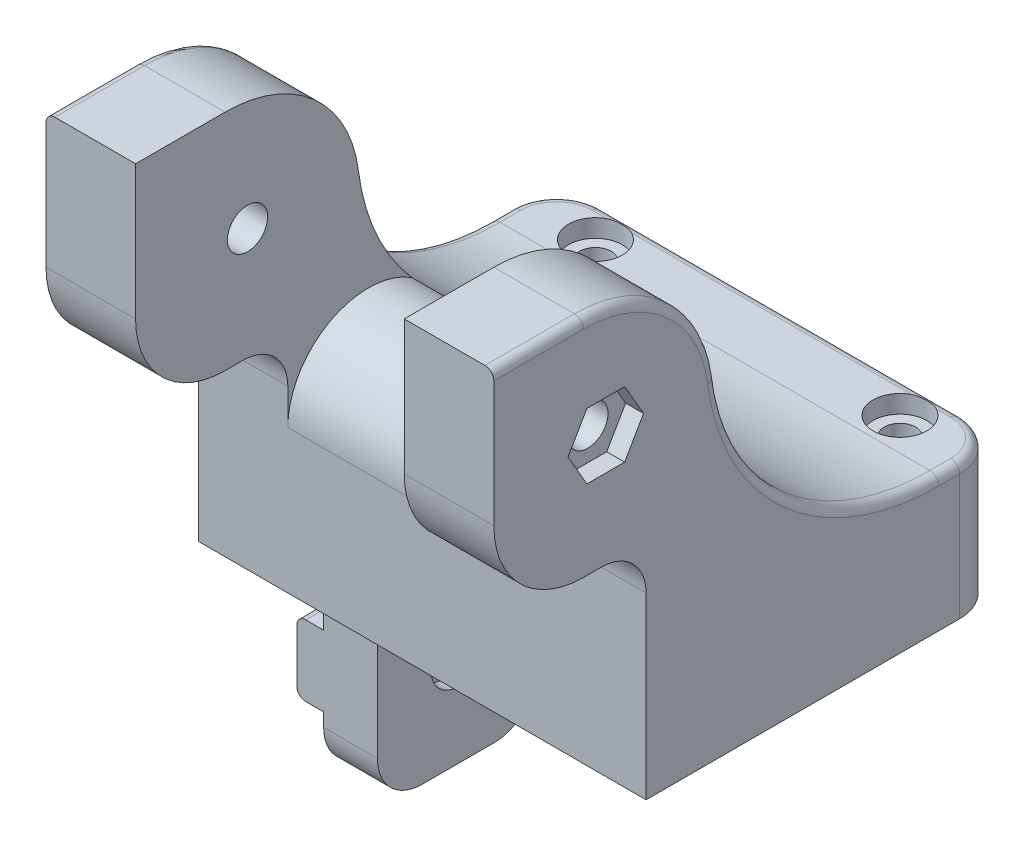
SolidWorks part; units mm, degrees
ref_plane "Alzado" through (0, 0, 0) normal (0, 0, 1) x (1, 0, 0)
ref_plane "Planta" through (0, 0, 0) normal (0, 1, 0) x (1, 0, 0)
ref_plane "Vista lateral" through (0, 0, 0) normal (1, 0, 0) x (0, 0, -1)
sketch "Croquis1" plane through (0, 0, 0) normal (0, 1, 0) x (1, 0, 0)
  line L1 (0, 0) -> (50, 0)
  line L2 (0, 0) -> (0, 40)
  line L3 (0, 40) -> (50, 40)
  line L4 (50, 0) -> (50, 40)
  dimension "D1" = 50
  dimension "D2" = 40
extrude "Saliente-Extruir1" add sketch "Croquis1" along normal blind 25
sketch "Croquis4" plane through (0, 25, 0) normal (0, 1, 0) x (1, 0, 0)
  line L0 (0, 40) -> (0, 0) construction
  line L1 (0, 8) -> (10, 8)
  line L2 (0, 8) -> (0, -17)
  line L3 (0, -17) -> (10, -17)
  line L4 (10, 8) -> (10, -17)
  line L5 (50, 0) -> (50, 40) construction
  line L6 (50, 8) -> (40, 8)
  line L7 (50, 8) -> (50, -17)
  line L8 (50, -17) -> (40, -17)
  line L9 (40, 8) -> (40, -17)
  line L10 (50, 40) -> (0, 40) construction
  dimension "D1" = 10
  dimension "D2" = 10
  dimension "D3" = 25
  dimension "D4" = 25
  dimension "D5" = 32
  dimension "D6" = 32
extrude "Saliente-Extruir3" add sketch "Croquis4" along normal blind 25
sketch "Croquis5" plane through (50, 0, 0) normal (1, 0, 0) x (0, 0, -1)
  line L0 (8, 50) -> (-17, 25) construction
  circle A0 centre (-4.5, 37.5) radius 2.25
  dimension "D1" = 4.5
extrude "Cortar-Extruir2" cut sketch "Croquis5" against normal up to surface (50 mm away) up to face at (0, 25, -7.75)
fillet "Redondeo4" radius 15 2 edges at (5, 50, -8) (45, 50, -8)
fillet "Redondeo5" radius 10 2 edges at (5, 25, 17) (45, 25, 17)
fillet "Redondeo6" radius 9 1 edges at (25, 25, 0)
sketch "Croquis6" plane through (0, 25, 0) normal (0, 1, 0) x (1, 0, 0)
  line L4 (0, 40) -> (0, 9)
  line L5 (0, 9) -> (50, 9)
  line L6 (50, 9) -> (50, 40)
  line L7 (50, 40) -> (0, 40)
  line L8 (0, 40) -> (0, 9)
  line L9 (0, 9) -> (50, 9)
  line L10 (50, 9) -> (50, 40)
  line L11 (50, 40) -> (0, 40)
  dimension "D1" = 0
extrude "Cortar-Extruir3" cut sketch "Croquis6" against normal blind 10
sketch "Croquis7" plane through (0, 0, -9) normal (0, 0, -1) x (-1, 0, 0)
  line L4 (0, 25) -> (-50, 25)
  line L5 (-50, 25) -> (-50, 15)
  line L6 (-50, 15) -> (0, 15)
  line L7 (0, 15) -> (0, 25)
  line L8 (0, 25) -> (-50, 25)
  line L9 (-50, 25) -> (-50, 15)
  line L10 (-50, 15) -> (0, 15)
  line L11 (0, 15) -> (0, 25)
  dimension "D1" = 0
extrude "Cortar-Extruir4" cut sketch "Croquis7" against normal up to surface (1 mm away) up to face at (5, 29.9721, -8)
fillet "Redondeo7" radius 25 1 edges at (25, 15, -8)
fillet "Redondeo8" radius 5 2 edges at (45, 25, 0) (5, 25, 0)
sketch "Croquis8" plane through (0, 15, 0) normal (0, 1, 0) x (1, 0, 0)
  line L0 (0, 36.3431) -> (50, 36.3431) construction
  line L1 (0, 40) -> (0, 32.6863) construction
  line L2 (50, 32.6863) -> (50, 40) construction
  circle A0 centre (8, 36.3431) radius 1.75
  circle A1 centre (42, 36.3431) radius 1.75
  dimension "D1" = 3.5
  dimension "D2" = 3.5
  dimension "D3" = 8
  dimension "D4" = 8
extrude "Cortar-Extruir5" cut sketch "Croquis8" against normal up to surface (15 mm away) up to face at (25, 0, -20)
sketch "Croquis9" plane through (0, 15, 0) normal (0, 1, 0) x (1, 0, 0)
  circle A0 centre (8, 36.3431) radius 3
  circle A1 centre (42, 36.3431) radius 3
  dimension "D1" = 6
  dimension "D2" = 6
extrude "Cortar-Extruir6" cut sketch "Croquis9" against normal blind 2
fillet "Redondeo9" radius 5 2 edges at (0, 7.5, -40) (50, 7.5, -40)
sketch "Croquis10" plane through (0, 0, 0) normal (0, -1, 0) x (1, 0, 0)
  line L0 (0, -35) -> (0, 0) construction
  line L1 (0, -32) -> (6, -32)
  line L2 (0, -32) -> (0, -14)
  line L3 (0, -14) -> (6, -14)
  line L4 (6, -32) -> (6, -14)
  line L5 (45, -40) -> (5, -40) construction
  dimension "D1" = 18
  dimension "D2" = 8
  dimension "D3" = 6
extrude "Saliente-Extruir4" add sketch "Croquis10" along normal blind 30
sketch "Croquis11" plane through (0, 0, 0) normal (-1, 0, 0) x (0, 0, 1)
  line L0 (-32, -30) -> (-32, 0) construction
  line L1 (-32, -23.5) -> (-14, -23.5)
  line L2 (-32, -23.5) -> (-32, -15.6)
  line L3 (-32, -15.6) -> (-14, -15.6)
  line L4 (-14, -23.5) -> (-14, -15.6)
  line L5 (-14, -30) -> (-14, 0) construction
  line L6 (-14, -30) -> (-32, -30) construction
  dimension "D1" = 6.5
  dimension "D2" = 7.9
extrude "Saliente-Extruir5" add sketch "Croquis11" along normal blind 3
fillet "Redondeo10" radius 1 2 edges at (-3, -23.5, -23) (-3, -15.6, -23)
sketch "Croquis12" plane through (-3, 0, 0) normal (-1, 0, 0) x (0, 0, 1)
  line L0 (-32, -19.55) -> (-14, -19.55) construction
  line L1 (-32, -16.6) -> (-32, -22.5) construction
  line L2 (-14, -22.5) -> (-14, -16.6) construction
  line L3 (-23, -22.5) -> (-23, -16.6) construction
  line L4 (-32, -22.5) -> (-14, -22.5) construction
  line L5 (-14, -16.6) -> (-32, -16.6) construction
  circle A0 centre (-23, -19.55) radius 1.75
  point P8 (-23, -19.55)
  dimension "D1" = 3.5
extrude "Cortar-Extruir7" cut sketch "Croquis12" against normal up to surface (9 mm away) up to face at (6, -15, -23)
sketch "Croquis13" plane through (6, 0, 0) normal (1, 0, 0) x (0, 0, -1)
  circle A0 centre (23, -19.55) radius 3
  dimension "D1" = 6
extrude "Cortar-Extruir8" cut sketch "Croquis13" against normal blind 1.5
sketch "Croquis16" plane through (0, 0, 0) normal (0, -1, 0) x (1, 0, 0)
  line L0 (25, -40) -> (25, 0) construction
  line L1 (45, -40) -> (5, -40) construction
  line L2 (0, 0) -> (50, 0) construction
  circle A0 centre (25, -25.3431) radius 1.75
  circle A1 centre (8, -36.3431) radius 1.75 construction
  dimension "D1" = 3.5
  dimension "D2" = 11
extrude "Cortar-Extruir9" cut sketch "Croquis16" against normal through all
ref_plane "Plano1" through (0, 20, 0) normal (0, 1, 0) x (1, 0, 0)
sketch "Croquis17" plane through (0, 20, 0) normal (0, 1, 0) x (1, 0, 0)
  circle A0 centre (25, 25.3431) radius 3
  dimension "D1" = 6
extrude "Cortar-Extruir10" cut sketch "Croquis17" against normal blind 5.5
fillet "Redondeo11" radius 5 2 edges at (3, -30, -14) (3, -30, -32)
fillet "Redondeo12" radius 1 11 edges at (50, 50, 12) (50, 46.25, -2.9216) (50, 21.25, -16.1503) (50, 15, -33.8431) (48.5355, 15, -38.5355) (0, 50, 12) (0, 46.25, -2.9216) (0, 21.25, -16.1503) (0, 15, -33.8431) (1.4645, 15, -38.5355) (25, 15, -40)
sketch "Croquis18" plane through (0, 0, 0) normal (-1, 0, 0) x (0, 0, 1)
  circle A0 centre (4.5, 37.5) radius 3.55
  dimension "D1" = 7.1
extrude "Cortar-Extruir11" cut sketch "Croquis18" against normal blind 2
sketch "Croquis19" plane through (50, 0, 0) normal (1, 0, 0) x (0, 0, -1)
  line L0 (-7, 49) -> (-17, 49) construction
  line L1 (-0.2853, 37.5) -> (-2.3927, 41.15)
  line L2 (-2.3927, 41.15) -> (-6.6073, 41.15)
  line L3 (-6.6073, 41.15) -> (-8.7147, 37.5)
  line L4 (-8.7147, 37.5) -> (-6.6073, 33.85)
  line L5 (-6.6073, 33.85) -> (-2.3927, 33.85)
  line L6 (-2.3927, 33.85) -> (-0.2853, 37.5)
  circle A0 centre (-4.5, 37.5) radius 3.65 construction
  dimension "D1" = 7.3
extrude "Cortar-Extruir12" cut sketch "Croquis19" against normal blind 2
